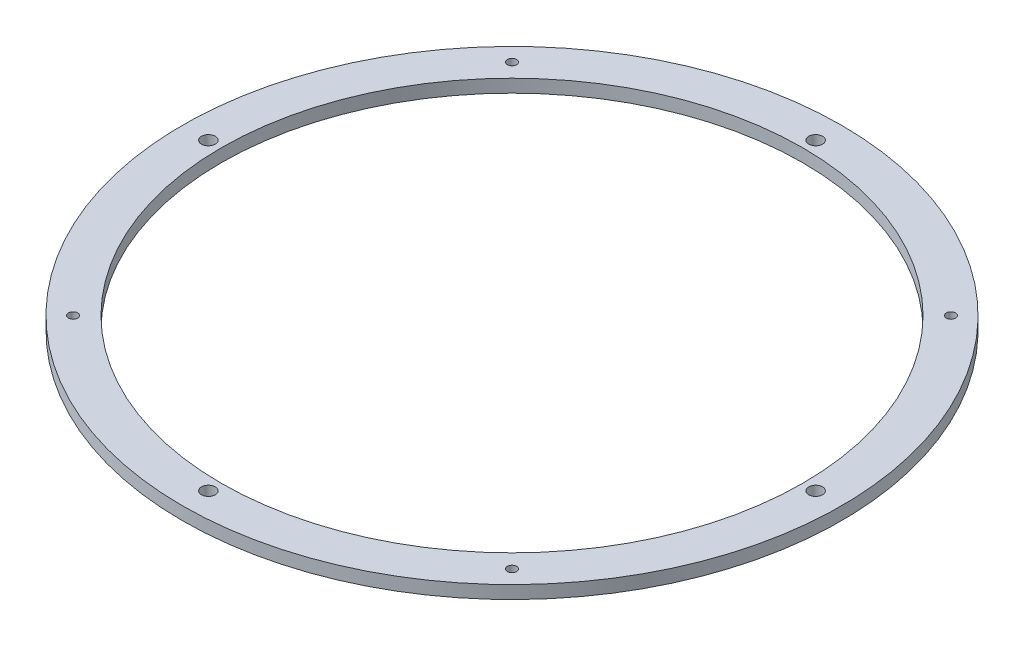
SolidWorks part; units mm, degrees
material "Pine"
ref_plane "Front Plane" through (0, 0, 0) normal (0, 0, 1) x (1, 0, 0)
ref_plane "Top Plane" through (0, 0, 0) normal (0, 1, 0) x (1, 0, 0)
ref_plane "Right Plane" through (0, 0, 0) normal (1, 0, 0) x (0, 0, -1)
sketch "Sketch1" plane through (0, 0, 0) normal (0, 1, 0) x (1, 0, 0)
  circle A0 centre (0, 0) radius 161.4
  circle A1 centre (0, 0) radius 136
  circle A3 centre (0, 0) radius 148.7 construction
  circle A4 centre (0, 0) radius 142.35
  dimension "D1" = 25.4
  dimension "D2" = 272
  dimension "D3" = 12.7
  dimension "D4" = 6.35
extrude "Boss-Extrude1" add sketch "Sketch1" along normal blind 6.35 contours A0 A4 region at (-156.8349, 0, 0)
sketch "Sketch2" plane through (0, 6.35, 0) normal (0, 1, 0) x (1, 0, 0)
  line L0 (0, 0) -> (0, -161.4) construction
  circle A1 centre (0, 0) radius 161.4 construction
  point P6 (0, -148.7)
  dimension "D1" = 12.7
hole_wizard "1/4 Clearance Hole1" positions "Sketch2" profile "Sketch3" hole size "1/4" standard "ANSI Inch" end condition through all
sketch "Sketch3" plane through (0, 6.35, 148.7) normal (1, 0, 0) x (0, 0, 1)
  line L0 (0, 0) -> (0, 6.35)
  line L1 (0, 6.35) -> (3.3782, 6.35)
  line L2 (3.3782, 6.35) -> (3.3782, 0)
  line L5 (3.3782, 0) -> (0, 0)
  line L11 (0, -6.35) -> (0, 107.95) construction
  dimension "Thru Hole Dia." = 6.7564
  dimension "Thru Hole Depth" = 6.35
pattern_circular "CirPattern1" count 4 every 90 about axis through (0, 6.35, 0) along (0, -1, 0) of "1/4 Clearance Hole1"
sketch "Sketch4" plane through (0, 6.35, 0) normal (0, 1, 0) x (1, 0, 0)
  line L0 (0, 0) -> (-107.4802, 107.4802) construction
  line L1 (-148.7, 0) -> (0, 0) construction
  dimension "D1" = 45
  dimension "D2" = 152
hole_wizard "M4 Clearance Hole1" positions "Sketch5" profile "Sketch6" hole size "M4" standard "ANSI Metric" end condition through all
sketch "Sketch5" plane through (0, 6.35, 0) normal (0, 1, 0) x (1, 0, 0)
  point P0 (-107.4802, 107.4802)
sketch "Sketch6" plane through (-107.4802, 6.35, -107.4802) normal (1, 0, 0) x (0, 0, 1)
  line L0 (0, 0) -> (0, 6.35)
  line L1 (0, 6.35) -> (2.25, 6.35)
  line L2 (2.25, 6.35) -> (2.25, 0)
  line L5 (2.25, 0) -> (0, 0)
  line L11 (0, -6.35) -> (0, 107.95) construction
  dimension "Thru Hole Dia." = 4.5
  dimension "Thru Hole Depth" = 6.35
pattern_circular "CirPattern2" count 4 over 360 about axis through (0, 6.35, 0) along (0, -1, 0) of "M4 Clearance Hole1" reverse direction yes
